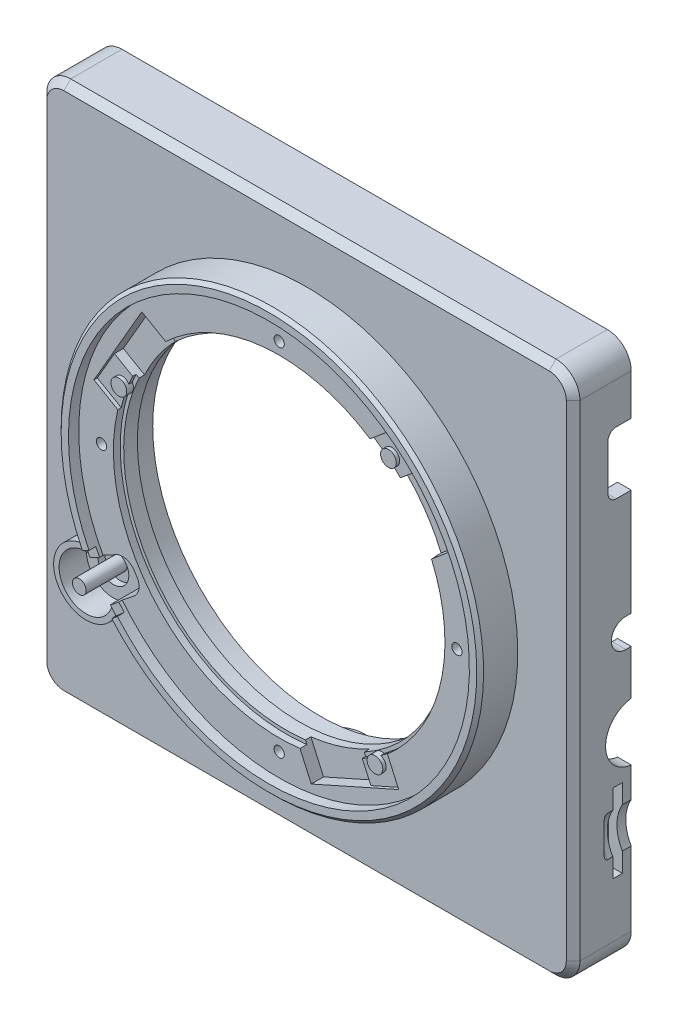
SolidWorks part; units mm, degrees
ref_plane "前视基准面" through (0, 0, 0) normal (0, 0, 1) x (1, 0, 0)
ref_plane "上视基准面" through (0, 0, 0) normal (0, 1, 0) x (1, 0, 0)
ref_plane "右视基准面" through (0, 0, 0) normal (1, 0, 0) x (0, 0, -1)
other "Configuration Table"
sketch "草图1" plane through (0, 0, 0) normal (0, 0, 1) x (1, 0, 0)
  line L1 (-39, -39) -> (39, -39)
  line L2 (-39, -39) -> (-39, 39)
  line L3 (-39, 39) -> (39, 39)
  line L4 (39, -39) -> (39, 39)
  line L5 (-39, -39) -> (39, 39) construction
  line L6 (-39, 39) -> (39, -39) construction
  circle A0 centre (0, 0) radius 23.75
  point P0 (0, 0)
  dimension "D2" = 47.5
  dimension "D1" = 78
extrude "凸台-拉伸1" add sketch "草图1" against normal blind 2
sketch "草图2" plane through (0, 0, 0) normal (0, 0, 1) x (1, 0, 0)
  circle A0 centre (0, 0) radius 23.75
  circle A1 centre (0, 0) radius 23.75 construction
  circle A2 centre (0, 0) radius 30.9
  dimension "D1" = 61.8
extrude "凸台-拉伸2" add sketch "草图2" along normal blind 4
sketch "草图3" plane through (0, 0, -2) normal (0, 0, -1) x (-1, 0, 0)
  line L0 (35.5, 32) -> (35.5, -32)
  line L1 (-39, -39) -> (39, -39)
  line L2 (-39, -39) -> (-39, 39)
  line L3 (-39, 39) -> (39, 39)
  line L4 (39, -39) -> (39, 39)
  line L5 (-39, -39) -> (39, 39) construction
  line L6 (-39, 39) -> (39, -39) construction
  line L7 (-37, -37) -> (37, -37)
  line L8 (-37, -37) -> (-37, 37)
  line L9 (-37, 37) -> (37, 37)
  line L10 (37, -37) -> (37, 37)
  line L11 (-37, -37) -> (37, 37) construction
  line L12 (-37, 37) -> (37, -37) construction
  line L13 (-37, 37) -> (-32, 37)
  line L14 (-37, 37) -> (-37, 32)
  line L15 (-37, 32) -> (-32, 32)
  line L16 (-32, 37) -> (-32, 32)
  line L17 (37, 37) -> (32, 37)
  line L18 (37, 37) -> (37, 32)
  line L19 (37, 32) -> (32, 32)
  line L20 (32, 37) -> (32, 32)
  line L21 (-37, -37) -> (-32, -37)
  line L22 (-37, -37) -> (-37, -32)
  line L23 (-37, -32) -> (-32, -32)
  line L24 (-32, -37) -> (-32, -32)
  line L25 (37, -37) -> (32, -37)
  line L26 (37, -37) -> (37, -32)
  line L27 (37, -32) -> (32, -32)
  line L28 (32, -37) -> (32, -32)
  point P0 (0, 0)
  point P7 (0, 0)
  line M23 (-39, 39) -> (-39, -39)
  line M24 (-39, -39) -> (39, -39)
  line M25 (39, -39) -> (39, 39)
  line M26 (39, 39) -> (-39, 39)
  dimension "D1" = 2
  dimension "D2" = 5
  dimension "D3" = 1.5
extrude "凸台-拉伸3" add sketch "草图3" along normal blind 6.5 contours L10 L7 L8 L9 M26 M23 M24 M25 | L16 L9 L8 L15 | L9 L20 L19 L10 | L28 L7 L10 L27 | L7 L24 L23 L8 | L27 L10 L19 L0 region at (-36.25, 0, -2) region at (-34.5, 34.5, -2) region at (-34.5, -34.5, -2) region at (34.5, 34.5, -2) region at (34.5, -34.5, -2) region at (37.8969, 0, -2)
sketch "草图4" plane through (0, 0, 4) normal (0, 0, 1) x (1, 0, 0)
  line L0 (0, 26) -> (0, -26) construction
  line L1 (-26, 0) -> (26, 0) construction
  circle A0 centre (0, 0) radius 26 construction
  circle A1 centre (0, 26) radius 0.75
  circle A2 centre (26, 0) radius 0.75
  circle A3 centre (0, -26) radius 0.75
  circle A4 centre (-26, 0) radius 0.75
  dimension "D2" = 52
  dimension "D3" = 1.5
extrude "切除-拉伸1" cut sketch "草图4" against normal blind 5
sketch "草图5" plane through (0, 0, 4) normal (0, 0, 1) x (1, 0, 0)
  line L0 (-15.4397, 0) -> (13.8511, 0) construction
  line L1 (-27.9748, -13.7193) -> (-23.5593, -20.3904)
  line L2 (-23.5593, -20.3904) -> (0, 0) construction
  line L3 (0, 0) -> (-27.9748, -13.7193) construction
  line L4 (-25.7671, -17.0549) -> (0, 0) construction
  line L5 (-27.9748, -13.7193) -> (-26.8884, -13.1865)
  line L6 (-26.8884, -13.1865) -> (-26.2006, -14.2257)
  line L7 (-26.2006, -14.2257) -> (0, 0) construction
  line L8 (0, 0) -> (-23.3322, -18.5593) construction
  line L9 (-23.3322, -18.5593) -> (-22.6444, -19.5985)
  line L10 (-22.6444, -19.5985) -> (-23.5593, -20.3904)
  line L11 (-26.2006, -14.2257) -> (-23.8565, -12.953)
  line L12 (-21.2344, -13.6068) -> (-20.822, -14.2298)
  line L13 (-21.2448, -16.8989) -> (-23.3322, -18.5593)
  circle A0 centre (0, 0) radius 30.9 construction
  arc A1 (-20.822, -14.2298) -> (-21.2448, -16.8989) centre (-22.4898, -15.3336) cw
  arc A2 (-23.8565, -12.953) -> (-21.2344, -13.6068) centre (-22.9021, -14.7106) cw
  point P17 (-19.8105, -15.758)
  point P20 (-22.2459, -12.0785)
  dimension "D6" = 2
  dimension "D1" = 33.5
  dimension "D2" = 8
  dimension "D3" = 5
  dimension "D4" = 1.2
  dimension "D5" = 4.5
extrude "切除-拉伸2" cut sketch "草图5" against normal blind 4
sketch "草图8" plane through (0, 0, 4) normal (0, 0, 1) x (1, 0, 0)
  line L0 (-27.7433, -13.6058) -> (-26.3292, -12.9123)
  line L1 (-23.3644, -20.2217) -> (-22.1735, -19.191)
  circle A0 centre (0, 0) radius 30.9
  circle A1 centre (0, 0) radius 29.325
  arc A2 (-23.3644, -20.2217) -> (-27.7433, -13.6058) centre (0, 0) ccw construction
  line M27 (-27.7433, -13.6058) -> (-26.8884, -13.1865)
  line M35 (-22.6444, -19.5985) -> (-23.3644, -20.2217)
  arc M36 (-23.3644, -20.2217) -> (-27.7433, -13.6058) centre (0, 0) ccw
  dimension "D1" = 58.65
extrude "凸台-拉伸5" add sketch "草图8" along normal blind 1.5 contours A1 L1 L0 M35 M36 M27 region at (-6.7861, 29.2491, 4)
chamfer "倒角1" distance 0.5 angle 45 1 edges at (25.7671, 17.0549, 5.5)
sketch "草图9" plane through (0, 0, -2) normal (0, 0, -1) x (-1, 0, 0)
  line L1 (-19, -20) -> (19, -20) construction
  line L2 (-19, -20) -> (-19, 20) construction
  line L3 (-19, 20) -> (19, 20) construction
  line L4 (19, -20) -> (19, 20) construction
  line L5 (-19, -20) -> (19, 20) construction
  line L6 (-19, 20) -> (19, -20) construction
  circle A0 centre (-19, -20) radius 0.8
  circle A1 centre (-19, -20) radius 1.65
  circle A2 centre (-19, 20) radius 0.8
  circle A3 centre (-19, 20) radius 1.65
  circle A4 centre (19, 20) radius 0.8
  circle A5 centre (19, 20) radius 1.65
  point P0 (0, 0)
  dimension "D2" = 1.6
  dimension "D3" = 3.3
  dimension "D1" = 38
  dimension "D4" = 40
extrude "凸台-拉伸6" add sketch "草图9" along normal blind 2.1
extrude "切除-拉伸4" cut sketch "草图9<2>" against normal blind 2 contours A2 | A4 | A0 region at (19, -20, -2) region at (19, 20, -2) region at (-19, 20, -2)
sketch "草图9<2>" plane through (0, 0, -2) normal (0, 0, -1) x (-1, 0, 0) same geometry as "草图9"
sketch "草图10" plane through (0, 0, -8.5) normal (0, 0, -1) x (-1, 0, 0)
  line L0 (39, 39) -> (-39, 39) construction
  line L1 (34.5, -34.5) -> (-34.5, -34.5) construction
  line L2 (34.5, -34.5) -> (34.5, 34.5) construction
  line L3 (34.5, 34.5) -> (-34.5, 34.5) construction
  line L4 (-34.5, -34.5) -> (-34.5, 34.5) construction
  line L5 (34.5, -34.5) -> (-34.5, 34.5) construction
  line L6 (34.5, 34.5) -> (-34.5, -34.5) construction
  circle A0 centre (-34.5, 34.5) radius 0.8
  circle A1 centre (34.5, 34.5) radius 0.8
  circle A2 centre (34.5, -34.5) radius 0.8
  circle A3 centre (-34.5, -34.5) radius 0.8
  point P0 (0, 0)
  dimension "D2" = 1.6
  dimension "D1" = 4.5
extrude "切除-拉伸5" cut sketch "草图10" against normal blind 4
sketch "草图18" plane through (0, -39, 0) normal (0, -1, 0) x (1, 0, 0)
  line L0 (39, -8.5) -> (-39, -8.5) construction
  line L1 (-39, 0) -> (39, 0) construction
  circle A0 centre (0, -4.25) radius 4.25
  circle A1 centre (0, -4.25) radius 2.5527
  dimension "D1" = 5.1054
extrude "凸台-拉伸9" add sketch "草图18" against normal blind 9 contours A1 | A0 A1 region at (-4.1298, -39, -4.25) region at (0, -39, -4.25)
extrude "切除-拉伸9" cut sketch "草图18<4>" against normal blind 7.5 contours A1 region at (0, -39, -4.25)
sketch "草图18<4>" plane through (0, -39, 0) normal (0, -1, 0) x (1, 0, 0) same geometry as "草图18"
sketch "草图30" plane through (0, 0, 0) normal (0, 0, 1) x (1, 0, 0)
  line L0 (-22.39, -14.8196) -> (0, 0) construction
  line L1 (-26.8884, -13.1865) -> (-28.4451, -13.9499)
  line L2 (-26.2006, -14.2257) -> (-27.3486, -14.8491)
  line L3 (-23.3322, -18.5593) -> (-24.3546, -19.3725)
  line L4 (-22.6444, -19.5985) -> (-23.9553, -20.7332)
  line L5 (-22.6444, -19.5985) -> (-23.3322, -18.5593)
  line L6 (-23.3644, -20.2217) -> (-22.6444, -19.5985) construction
  line L7 (-23.3322, -18.5593) -> (-21.2448, -16.8989) construction
  line L8 (-23.8565, -12.953) -> (-26.2006, -14.2257) construction
  line L9 (-27.2944, -13.3856) -> (-26.3292, -12.9123) construction
  line L10 (-26.8884, -13.1865) -> (-26.2006, -14.2257)
  line L11 (-20.822, -14.2298) -> (-21.2344, -13.6068) construction
  line L12 (-20.822, -14.2298) -> (-21.2344, -13.6068) construction
  circle A0 centre (-28.2462, -18.6958) radius 4.75
  circle A2 centre (-28.2462, -18.6958) radius 3.95
  point P3 (-21.0282, -13.9183)
  line M13 (-26.8884, -13.1865) -> (-27.7433, -13.6058)
  line M15 (-23.3644, -20.2217) -> (-22.6444, -19.5985)
  line M16 (-22.6444, -19.5985) -> (-23.3322, -18.5593)
  line M22 (-26.2006, -14.2257) -> (-26.8884, -13.1865)
  dimension "D2" = 9.5
  dimension "D3" = 7.9
  dimension "D1" = 33.873
extrude "凸台-拉伸10" add sketch "草图30" along normal blind 4 contours A0 L2 L1 M22 M13 | A0 L0 A2 L2 | L0 A0 L3 A2 | A0 L4 L3 M15 M16 region at (-27.1202, -13.7897, 0) region at (-27.418, -14.155, 0) region at (-23.2902, -19.5762, 0)
sketch "草图31" plane through (0, 0, 0) normal (0, 0, 1) x (1, 0, 0)
  circle A0 centre (-28.2462, -18.6958) radius 1
  circle A1 centre (-28.2462, -18.6958) radius 2.25
  dimension "D1" = 2
  dimension "D2" = 4.5
extrude "切除-拉伸19" cut sketch "草图31" against normal blind 1
sketch "草图32" plane through (0, 0, 0) normal (0, 0, 1) x (1, 0, 0)
  circle A0 centre (-28.2462, -18.6958) radius 1
  circle A1 centre (-28.2462, -18.6958) radius 1 construction
extrude "凸台-拉伸11" add sketch "草图32" along normal blind 5
sketch "草图33" plane through (0, 0, 4) normal (0, 0, 1) x (1, 0, 0)
  line L0 (-26.3292, -12.9123) -> (-27.7433, -13.6058)
  line L1 (-27.1554, -14.7442) -> (-25.7713, -13.9927)
  line L2 (-23.8565, -12.953) -> (-27.3486, -14.8491) construction
  line L3 (-23.8565, -12.953) -> (-27.3486, -14.8491) construction
  line L4 (-24.1826, -19.2357) -> (-22.95, -18.2552)
  line L5 (-24.3546, -19.3725) -> (-21.2448, -16.8989) construction
  line L6 (-22.1735, -19.191) -> (-23.3644, -20.2217)
  circle A0 centre (0, 0) radius 29.325
  circle A1 centre (0, 0) radius 30.9
  line M3 (-26.3292, -12.9123) -> (-27.7433, -13.6058)
  line M7 (-23.3644, -20.2217) -> (-22.1735, -19.191)
  line M10 (-27.3486, -14.8491) -> (-23.8565, -12.953)
  line M14 (-21.2448, -16.8989) -> (-24.3546, -19.3725)
extrude "凸台-拉伸12" add sketch "草图33" along normal blind 0.5 contours A1 A0 M3 M10 | A1 A0 M14 M7 region at (-26.7598, -13.8189, 4) region at (-23.1762, -19.233, 4)
fillet "圆角5" radius 1 2 edges at (-3.6056, -33.5, -2) (3.6056, -33.5, -2)
fillet "圆角2" radius 1.5 12 edges at (37, -32, -5.25) (32, -37, -5.25) (-32, -37, -5.25) (-32, -32, -5.25) (-32, 37, -5.25) (32, -32, -5.25) (-32, 32, -5.25) (32, 37, -5.25) (37, 32, -5.25) (32, 32, -5.25) (-35.5, -32, -5.25) (-35.5, 32, -5.25)
fillet "圆角3" radius 3.5 4 edges at (39, -39, -4.25) (-39, -39, -4.25) (-39, 39, -4.25) (39, 39, -4.25)
chamfer "倒角2" distance 1 angle 45 8 edges at (0, -39, 0) (37.9749, -37.9749, 0) (-37.9749, -37.9749, 0) (39, 0, 0) (-39, 0, 0) (37.9749, 37.9749, 0) (-37.9749, 37.9749, 0) (0, 39, 0)
sketch "草图11" plane through (0, 0, 4) normal (0, 0, 1) x (1, 0, 0)
  circle A0 centre (0, 0) radius 24.25
  dimension "D1" = 48.5
extrude "切除-拉伸6" cut sketch "草图11" against normal blind 1
sketch "草图19" plane through (-39, 0, 0) normal (-1, 0, 0) x (0, 0, 1)
  line L0 (-8.5, -35.5) -> (-8.5, 35.5) construction
  line L1 (-8.5, 30) -> (-2.5, 30)
  line L2 (-8.5, 30) -> (-8.5, -30)
  line L3 (-8.5, -30) -> (-2.5, -30)
  line L4 (-2.5, 30) -> (-2.5, -30)
  line L5 (-10.4781, 0) -> (-27.7758, 0) construction
  dimension "D1" = 6
  dimension "D2" = 60
extrude "切除-拉伸10" cut sketch "草图19" against normal blind 1.8
sketch "草图12" plane through (0, 0, -8.5) normal (0, 0, -1) x (-1, 0, 0)
  line L0 (-30.5, 37) -> (30.5, 37) construction
  line L1 (-14.5, 37) -> (14.5, 37)
  line L2 (-14.5, 37) -> (-14.5, 38)
  line L3 (-14.5, 38) -> (14.5, 38)
  line L4 (14.5, 37) -> (14.5, 38)
  line L10 (-30.5, -37) -> (-5.099, -37) construction
  line L11 (14.5, -37) -> (-14.5, -37)
  line L12 (14.5, -37) -> (14.5, -38)
  line L13 (14.5, -38) -> (-14.5, -38)
  line L14 (-14.5, -37) -> (-14.5, -38)
  line L20 (0, -4.6052) -> (0, 11.8131) construction
  line L21 (9.1859, 0) -> (-14.9207, 0) construction
  line L22 (-3.5, -37) -> (-3.5, -38)
  line L23 (3.5, -37) -> (3.5, -38)
  line M27 (30.5, -37) -> (0, -37)
  line M39 (-30.5, 37) -> (30.5, 37)
  dimension "D1" = 29
  dimension "D2" = 1
  dimension "D3" = 7
extrude "切除-拉伸7" cut sketch "草图12" against normal blind 1 contours L22 L11 L14 L13 | L23 L13 L12 M27 | L4 L3 L2 M39
sketch "草图21" plane through (0, 0, -2) normal (0, 0, -1) x (-1, 0, 0)
  circle A0 centre (0, 0) radius 24.5
  dimension "D1" = 49
extrude "切除-拉伸12" cut sketch "草图21" against normal blind 3
sketch "草图22" plane through (0, 0, 0) normal (0, 0, 1) x (1, 0, 0)
  text T0 "Sitina" font "Corbel" height 3.5
  text T1 "S1" font "Sylfaen" height 3.5
sketch "草图23" plane through (0, 0, -8.5) normal (0, 0, -1) x (-1, 0, 0)
  line L0 (35.5, 30.5) -> (35.5, -30.5) construction
  line L1 (35.5, 20) -> (37.2, 20)
  line L2 (35.5, 20) -> (35.5, 10.5)
  line L3 (35.5, 10.5) -> (37.2, 10.5)
  line L4 (37.2, 20) -> (37.2, 10.5)
  line L5 (37.2, -30) -> (37.2, 30) construction
  dimension "D1" = 9.5
  dimension "D2" = 10.5
extrude "切除-拉伸14" cut sketch "草图23" against normal blind 1
sketch "草图24" plane through (-35.5, 0, 0) normal (1, 0, 0) x (0, 0, -1)
  line L0 (4.7, -23.516) -> (4.7, -0.4558) construction
  line L1 (8.5, 10.5) -> (8.5, -30.5) construction
  line L2 (2, -30.5) -> (8.5, -30.5) construction
  line L3 (4.7, -25) -> (4.7, 0) construction
  circle A0 centre (4.7, -25) radius 0.65
  circle A1 centre (4.7, 0) radius 0.65
  circle A2 centre (4.7, 25) radius 0.65
  dimension "D2" = 1.3
  dimension "D1" = 3.8
  dimension "D3" = 5.5
  dimension "D5" = 25
  dimension "D4" = 3
extrude "切除-拉伸15" cut sketch "草图24" against normal blind 4.75
sketch "草图26" plane through (39, 0, 0) normal (1, 0, 0) x (0, 0, -1)
  line L0 (8.5, 35.5) -> (8.5, -35.5) construction
  line L1 (5.8, -27.5) -> (7.2, -27.5)
  line L2 (5.8, -27.5) -> (5.8, -16)
  line L3 (5.8, -16) -> (7.2, -16)
  line L4 (7.2, -27.5) -> (7.2, -16)
  line L5 (1, -35.5) -> (8.5, -35.5) construction
  line L6 (12.7, 2.7) -> (7.7, 2.7) construction
  line L7 (12.7, 0.6) -> (7.7, 0.6)
  line L8 (12.7, 4.8) -> (7.7, 4.8)
  line L9 (8.5, 29.5) -> (8.5, 20.4)
  line L12 (8.5, 35.5) -> (1, 35.5) construction
  line L13 (8.5, 20.4) -> (6.3, 20.4)
  line L14 (8.5, 29.5) -> (6.3, 29.5)
  line L15 (5.1, 28.3) -> (5.1, 21.6)
  circle A0 centre (9, -10.2) radius 4.25
  arc A1 (12.7, 0.6) -> (12.7, 4.8) centre (12.7, 2.7) ccw
  arc A2 (7.7, 4.8) -> (7.7, 0.6) centre (7.7, 2.7) ccw
  arc A5 (6.3, 29.5) -> (5.1, 28.3) centre (6.3, 28.3) ccw
  arc A6 (6.3, 20.4) -> (5.1, 21.6) centre (6.3, 21.6) cw
  point P10 (10.2, 2.7)
  dimension "D7" = 8.5
  dimension "D9" = 2.1
  dimension "D15" = 1.2
  dimension "D1" = 11.5
  dimension "D2" = 1.4
  dimension "D3" = 1.3
  dimension "D4" = 8
  dimension "D5" = 25.3
  dimension "D6" = 0.5
  dimension "D8" = 38.2
  dimension "D10" = 0.8
  dimension "D11" = 5
  dimension "D12" = 6
  dimension "D13" = 9.1
  dimension "D14" = 3.4
extrude "切除-拉伸17" cut sketch "草图26" against normal blind 10
sketch "草图29" plane through (0, 0, -2) normal (0, 0, -1) x (-1, 0, 0)
  line L0 (0, 6.6658) -> (0, 18.0542) construction
  line L1 (6.3625, 0) -> (19.1145, 0) construction
  circle A0 centre (-15, 22) radius 0.8
  circle A1 centre (15, -22) radius 0.8
  dimension "D1" = 1.6
  dimension "D2" = 15
  dimension "D3" = 15
  dimension "D4" = 22
  dimension "D5" = 22
extrude "切除-拉伸18" cut sketch "草图29" against normal blind 3
fillet "圆角6" radius 0.5 2 edges at (-27.7433, -13.6058, 2) (-23.3644, -20.2217, 2)
sketch "草图34" plane through (0, 0, 4) normal (0, 0, 1) x (1, 0, 0)
  line L0 (15.2413, -17.0225) -> (2.4517, -22.7168)
  line L1 (2.4517, -22.7168) -> (4.6888, -27.7413)
  line L2 (4.6888, -27.7413) -> (17.4784, -22.047)
  line L3 (17.4784, -22.047) -> (15.2413, -17.0225)
  line L4 (0, -1000) -> (0, 49000) construction
  line L5 (0, 0) -> (8.8465, -19.8696) construction
  line L6 (10.6736, -19.0561) -> (12.9107, -24.0806)
  line L7 (12.162, 19.3429) -> (21.161, 8.6183)
  line L8 (21.161, 8.6183) -> (25.3742, 12.1537)
  line L9 (25.3742, 12.1537) -> (16.3752, 22.8783)
  line L10 (16.3752, 22.8783) -> (12.162, 19.3429)
  line L11 (-15.3361, 16.9372) -> (-22.3361, 4.8128)
  line L12 (-22.3361, 4.8128) -> (-27.0992, 7.5628)
  line L13 (-27.0992, 7.5628) -> (-20.0992, 19.6872)
  line L14 (-20.0992, 19.6872) -> (-15.3361, 16.9372)
  line L15 (-24.5992, 11.8929) -> (-19.8361, 9.1429)
  line L16 (15.3759, 15.5127) -> (19.5891, 19.0481)
  line L17 (-18.8361, 10.875) -> (0, 0)
  line L18 (0, 0) -> (16.6615, 13.9806)
  circle A0 centre (0, 0) radius 21.75 construction
  point P5 (8.8465, -19.8696)
  point P19 (-18.8361, 10.875)
  point P22 (16.6615, 13.9806)
  circle M8 centre (0, 0) radius 24.25
  dimension "D1" = 43.5
  dimension "D2" = 14
  dimension "D3" = 5.5
  dimension "D4" = 24
  dimension "D5" = 5
  dimension "D6" = 5
  dimension "D7" = 5
  dimension "D8" = 60
  dimension "D9" = 50
extrude "切除-拉伸20" cut sketch "草图34" against normal blind 0.5 contours L6 L2 L3 M8 | L0 L6 L3 M8 | L16 L9 L10 M8 | L7 L16 L10 M8 | L15 L13 L12 M8 | L15 L12 L11 M8 region at (13.2013, -19.0643, 4) region at (14.5891, -21.424, 4) region at (-21.8858, 7.6638, 4) region at (-24.3955, 8.7571, 4) region at (16.5728, 19.9292, 4) region at (14.687, 17.9447, 4)
extrude "切除-拉伸21" cut sketch "草图34<3>" against normal blind 1.8 contours L6 L0 L1 M8 | L6 L1 L2 M8 | L13 L15 L14 M8 | L15 L11 L14 M8 | L16 L8 L9 M8 | L16 L7 L8 M8 region at (7.314, -21.7939, 4) region at (7.9313, -24.492, 4) region at (21.357, 14.375, 4) region at (18.9336, 13.0379, 4) region at (-18.7273, 13.3326, 4) region at (-20.8126, 15.1525, 4)
sketch "草图34<3>" plane through (0, 0, 4) normal (0, 0, 1) x (1, 0, 0) same geometry as "草图34"
sketch "草图35" plane through (0, 0, 3) normal (0, 0, 1) x (1, 0, 0)
  line L0 (17.4784, -22.047) -> (15.8383, -18.3633) construction
  line L1 (12.9107, -24.0806) -> (17.4784, -22.047) construction
  line L2 (25.3742, 12.1537) -> (16.3752, 22.8783) construction
  line L3 (-27.0992, 7.5628) -> (-20.0992, 19.6872) construction
  line L4 (-23.6071, 5.5467) -> (-27.0992, 7.5628) construction
  line L5 (16.3752, 22.8783) -> (13.2863, 20.2864) construction
  circle A0 centre (14.005, -20.6379) radius 1.15
  circle A1 centre (15.9781, 19.151) radius 1.15
  circle A2 centre (-23.4609, 8.4645) radius 1.15
  dimension "D1" = 2.3
  dimension "D2" = 2.6
  dimension "D3" = 2.7
  dimension "D4" = 2.7
  dimension "D5" = 2.7
  dimension "D6" = 2.6
  dimension "D7" = 2.6
extrude "凸台-拉伸13" add sketch "草图35" along normal blind 1
sketch "草图36" plane through (0, 0, -8.5) normal (0, 0, -1) x (-1, 0, 0)
  line L1 (-1040.6187, -21.75) -> (48959.3813, -21.75) construction
  line L2 (-39, -27.5) -> (-39, -16) construction
  line L3 (-39, -14.4205) -> (-39, -35.5) construction
  circle A0 centre (-44, -21.75) radius 5.8
  point P5 (-39, -21.75)
  dimension "D2" = 11.6
  dimension "D1" = 5
extrude "切除-拉伸22" cut sketch "草图36" against normal blind 4
fillet "圆角7" radius 0.5 1 edges at (38.2, -21.75, -4.5)
sketch "草图37" plane through (0, -39, 0) normal (0, -1, 0) x (1, 0, 0)
  line L0 (-29, -6) -> (-17, -6) construction
  line L1 (-29, -5) -> (-17, -5)
  line L2 (-29, -7) -> (-17, -7)
  line L3 (35.5, -8.5) -> (-35.5, -8.5) construction
  line L4 (-39, -8.5) -> (-39, -1) construction
  line L5 (0, -1000) -> (0, 49000) construction
  line L6 (29, -6) -> (17, -6) construction
  line L7 (29, -5) -> (17, -5)
  line L8 (29, -7) -> (17, -7)
  arc A0 (-29, -5) -> (-29, -7) centre (-29, -6) ccw
  arc A1 (-17, -7) -> (-17, -5) centre (-17, -6) ccw
  arc A2 (29, -5) -> (29, -7) centre (29, -6) cw
  arc A3 (17, -7) -> (17, -5) centre (17, -6) cw
  point P2 (-23, -6)
  point P16 (23, -6)
  dimension "D4" = 1
  dimension "D1" = 2.5
  dimension "D2" = 10
  dimension "D3" = 12
extrude "切除-拉伸23" cut sketch "草图37" against normal blind 4
